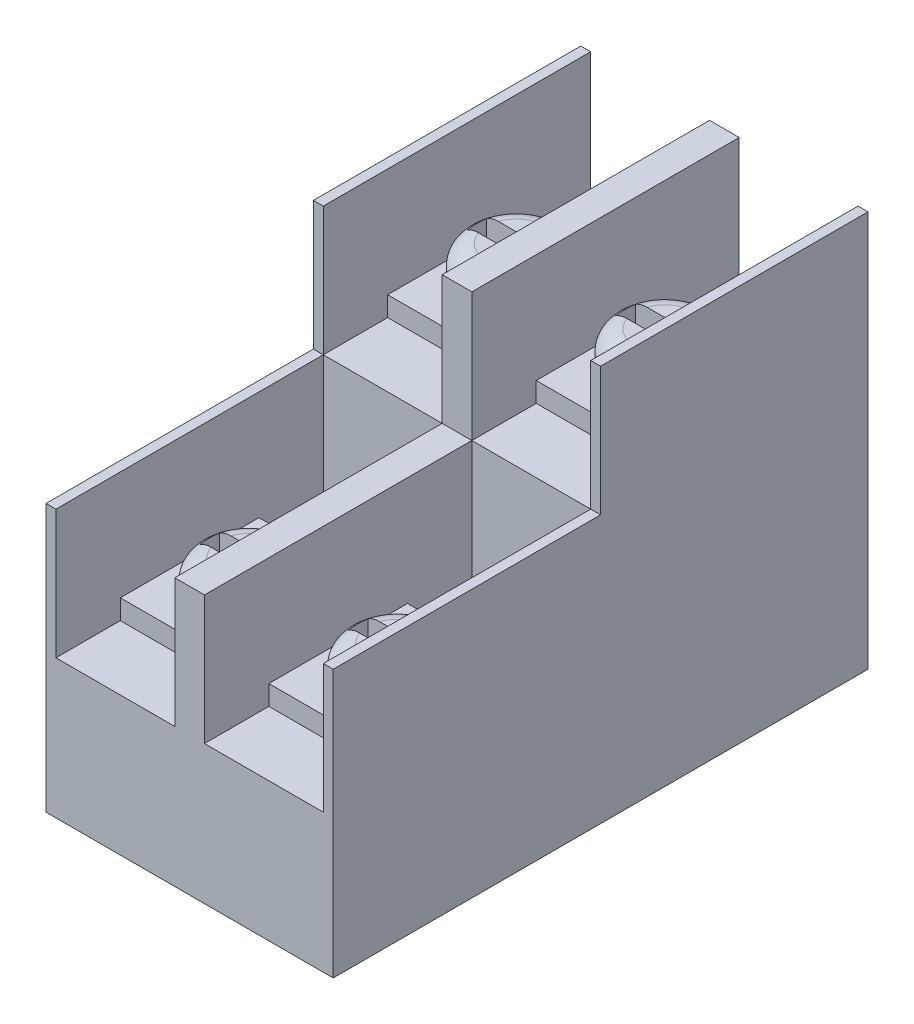
SolidWorks part; units mm, degrees
ref_plane "前视基准面" through (0, 0, 0) normal (0, 0, 1) x (1, 0, 0)
ref_plane "上视基准面" through (0, 0, 0) normal (0, 1, 0) x (1, 0, 0)
ref_plane "右视基准面" through (0, 0, 0) normal (1, 0, 0) x (0, 0, -1)
sketch "草图2" plane through (0, 0, 0) normal (0, 1, 0) x (1, 0, 0)
  line L1 (-7.25, -13.5) -> (7.25, -13.5)
  line L2 (-7.25, -13.5) -> (-7.25, 13.5)
  line L3 (-7.25, 13.5) -> (7.25, 13.5)
  line L4 (7.25, -13.5) -> (7.25, 13.5)
  line L5 (-7.25, -13.5) -> (7.25, 13.5) construction
  line L6 (-7.25, 13.5) -> (7.25, -13.5) construction
  point P0 (0, 0)
  dimension "D1" = 14.5
  dimension "D2" = 27
extrude "凸台-拉伸1" add sketch "草图2" along normal blind 20
sketch "草图3" plane through (7.25, 0, 0) normal (1, 0, 0) x (0, 0, -1)
  line L0 (0, 20) -> (0, 13.5)
  line L1 (-13.5, 20) -> (13.5, 20) construction
  line L2 (0, 13.5) -> (-13.5, 13.5)
  line L3 (-13.5, 20) -> (-13.5, 0) construction
  line L4 (-13.5, 13.5) -> (-13.5, 20)
  line L5 (-13.5, 20) -> (0, 20)
  line L6 (-13.5, 0) -> (13.5, 0) construction
  dimension "D1" = 13.5
extrude "切除-拉伸1" cut sketch "草图3" against normal through all
sketch "草图5" plane through (0, 20, 0) normal (0, 1, 0) x (1, 0, 0)
  line L0 (-7.25, 13.5) -> (-7.25, 0) construction
  line L1 (0.75, 13.5) -> (0.75, 0)
  line L2 (7.25, 13.5) -> (-7.25, 13.5) construction
  line L3 (-7.25, 0) -> (7.25, 0) construction
  line L4 (0.75, 0) -> (6.75, 0)
  line L5 (6.75, 0) -> (6.75, 13.5)
  line L6 (6.75, 13.5) -> (0.75, 13.5)
  line L7 (7.25, 0) -> (7.25, 13.5) construction
  line L8 (-0.75, 0) -> (-6.75, 0)
  line L9 (-6.75, 0) -> (-6.75, 13.5)
  line L10 (-6.75, 13.5) -> (-0.75, 13.5)
  line L11 (-0.75, 13.5) -> (-0.75, 0)
  line L17 (0, -1000) -> (0, 49000) construction
  dimension "D1" = 0.5
  dimension "D2" = 6
  dimension "D3" = 0.5
  dimension "D4" = 6
extrude "切除-拉伸2" cut sketch "草图5" against normal blind 6.5
sketch "草图7" plane through (0, 13.5, 0) normal (0, 1, 0) x (1, 0, 0)
  line L0 (6.75, 0) -> (6.75, -13.5)
  line L1 (-7.25, -13.5) -> (7.25, -13.5) construction
  line L2 (6.75, -13.5) -> (0.75, -13.5)
  line L3 (0.75, -13.5) -> (0.75, 0)
  line L4 (0.75, 0) -> (6.75, 0)
  line L5 (-6.75, 13.5) -> (-6.75, 0) construction
  line L6 (-6.75, -13.5) -> (-0.75, -13.5)
  line L7 (-6.75, 0) -> (-6.75, -13.5)
  line L8 (-0.75, 0) -> (-6.75, 0)
  line L9 (-0.75, -13.5) -> (-0.75, 0)
extrude "切除-拉伸4" cut sketch "草图7" against normal blind 6.5
sketch "草图8" plane through (0, 13.5, 0) normal (0, 1, 0) x (1, 0, 0)
  line L0 (-6.75, 13.5) -> (-6.75, 0) construction
  line L1 (-0.75, 0) -> (-0.75, 13.5) construction
  line L2 (-6.75, 10.25) -> (-0.75, 10.25)
  line L3 (-6.75, 10.25) -> (-6.75, 3.25)
  line L4 (-6.75, 3.25) -> (-0.75, 3.25)
  line L5 (-0.75, 10.25) -> (-0.75, 3.25)
  line L6 (0.75, 6.75) -> (13.2595, 6.75) construction
  line L7 (0.75, 13.5) -> (0.75, 0) construction
  line L9 (0.75, 10.25) -> (0.75, 3.25)
  line L10 (6.75, 3.25) -> (0.75, 3.25)
  line L11 (6.75, 10.25) -> (6.75, 3.25)
  line L12 (6.75, 10.25) -> (0.75, 10.25)
  line L13 (-3.75, 13.5) -> (-3.75, 1.5879) construction
  line L14 (-0.75, 13.5) -> (-6.75, 13.5) construction
  line L16 (6.75, 0) -> (6.75, 13.5) construction
  circle A0 centre (-3.75, 6.75) radius 1.75
  circle A1 centre (3.75, 6.75) radius 1.75
  point P29 (-0.75, 6.75)
  point P32 (3.75, 10.25)
  dimension "D2" = 3.5
  dimension "D1" = 7
extrude "凸台-拉伸3" add sketch "草图8" along normal blind 1
sketch "草图9" plane through (0, 7, 0) normal (0, 1, 0) x (1, 0, 0)
  line L0 (-6.75, 0) -> (-6.75, -13.5) construction
  line L1 (-6.75, -3.25) -> (-0.75, -3.25)
  line L2 (-6.75, -3.25) -> (-6.75, -10.25)
  line L3 (-6.75, -10.25) -> (-0.75, -10.25)
  line L4 (-0.75, -3.25) -> (-0.75, -10.25)
  line L5 (-0.75, -13.5) -> (-0.75, 0) construction
  line L6 (-6.75, 10.25) -> (-6.75, 3.25) construction
  line L7 (-3.75, 6.75) -> (-3.75, -14.6652) construction
  line L9 (0, 0) -> (-14.6212, 0) construction
  line L10 (-6.75, 3.25) -> (-0.75, 3.25) construction
  line L12 (6.75, -3.25) -> (6.75, -10.25)
  line L13 (6.75, -3.25) -> (0.75, -3.25)
  line L14 (0.75, -3.25) -> (0.75, -10.25)
  line L15 (6.75, -10.25) -> (0.75, -10.25)
  line L16 (0.75, 0) -> (0.75, -13.5) construction
  line L17 (6.75, -13.5) -> (6.75, 0) construction
  circle A0 centre (-3.75, -6.75) radius 1.75
  circle A1 centre (-3.75, 6.75) radius 1.75 construction
  circle A2 centre (3.75, -6.75) radius 1.75
  point P23 (-0.75, -6.75)
  point P38 (3.75, -3.25)
extrude "凸台-拉伸4" add sketch "草图9" along normal blind 1
sketch "草图10" plane through (0, 14.5, 0) normal (0, 1, 0) x (1, 0, 0)
  line L3 (0, 0) -> (0, 15.3782) construction
  circle A0 centre (3.75, 6.75) radius 2.5
  circle A1 centre (3.75, 6.75) radius 1.75 construction
  circle A2 centre (-3.75, 6.75) radius 2.5
  dimension "D1" = 5
extrude "凸台-拉伸5" add sketch "草图10" along normal blind 2
sketch "草图14" plane through (0, 8, 0) normal (0, 1, 0) x (1, 0, 0)
  line L0 (0, 0) -> (0, -10.3394) construction
  circle A0 centre (-3.75, -6.75) radius 2.5
  circle A1 centre (3.75, -6.75) radius 2.5
  dimension "D1" = 5
extrude "凸台-拉伸6" add sketch "草图14" along normal blind 1.5
sketch "草图15" plane through (0, 9.5, 0) normal (0, 1, 0) x (1, 0, 0)
  line L0 (3.25, -9.1995) -> (3.25, -7.25)
  line L1 (1.75, -6.25) -> (3.25, -6.25)
  line L2 (1.75, -6.25) -> (1.75, -7.25)
  line L3 (1.75, -7.25) -> (3.25, -7.25)
  line L4 (5.75, -6.25) -> (5.75, -7.25)
  line L5 (4.25, -4.3005) -> (4.25, -6.25)
  line L6 (-0.584, -6.75) -> (8.084, -6.75) construction
  line L7 (3.75, -10.7827) -> (3.75, -2.7173) construction
  line L8 (3.25, -6.25) -> (3.25, -4.3005)
  line L9 (4.25, -7.25) -> (4.25, -9.1995)
  line L10 (4.25, -7.25) -> (5.75, -7.25)
  line L11 (4.25, -6.25) -> (5.75, -6.25)
  line L13 (0, -1000) -> (0, 49000) construction
  line L14 (-3.75, -10.7827) -> (-3.75, -2.7173) construction
  line L15 (0.584, -6.75) -> (-8.084, -6.75) construction
  line L16 (-4.25, -6.25) -> (-5.75, -6.25)
  line L17 (-4.25, -7.25) -> (-5.75, -7.25)
  line L18 (-4.25, -7.25) -> (-4.25, -9.1995)
  line L19 (-3.25, -6.25) -> (-3.25, -4.3005)
  line L20 (-4.25, -4.3005) -> (-4.25, -6.25)
  line L21 (-5.75, -6.25) -> (-5.75, -7.25)
  line L22 (-1.75, -7.25) -> (-3.25, -7.25)
  line L23 (-1.75, -6.25) -> (-1.75, -7.25)
  line L24 (-1.75, -6.25) -> (-3.25, -6.25)
  line L25 (-3.25, -9.1995) -> (-3.25, -7.25)
  line L26 (0.75, 0) -> (0.75, -13.5) construction
  circle A0 centre (3.75, -6.75) radius 2.5 construction
  arc A1 (3.25, -9.1995) -> (4.25, -9.1995) centre (3.75, -6.75) ccw
  arc A3 (3.25, -4.3005) -> (4.25, -4.3005) centre (3.75, -6.75) cw
  arc A4 (-3.25, -4.3005) -> (-4.25, -4.3005) centre (-3.75, -6.75) ccw
  arc A5 (-3.25, -9.1995) -> (-4.25, -9.1995) centre (-3.75, -6.75) cw
  point P15 (3.75, -6.75)
  point P18 (3.75, -6.75)
  point P45 (0.75, -6.75)
  dimension "D1" = 4
  dimension "D2" = 1
  dimension "D3" = 1
fillet "圆角1" radius 1 4 edges at (-3.75, 16.5, -9.25) (3.75, 16.5, -4.25) (3.75, 9.5, 4.25) (-3.75, 9.5, 9.25)
extrude "切除-拉伸12" cut sketch "草图15" against normal blind 1.2
sketch "草图16" plane through (0, 16.5, 0) normal (0, 1, 0) x (1, 0, 0)
  line L0 (3.75, 6.75) -> (3.75, 9.8332) construction
  line L1 (3.75, 6.75) -> (10.8226, 6.75) construction
  line L2 (0, 0) -> (0, 17.5195) construction
  line L3 (-3.75, 6.75) -> (-10.8226, 6.75) construction
  line L4 (-3.75, 6.75) -> (-3.75, 9.8332) construction
  line L5 (-3.25, 7.25) -> (-1.75, 7.25)
  line L6 (-3.25, 9.1995) -> (-3.25, 7.25)
  line L7 (-4.25, 7.25) -> (-4.25, 9.1995)
  line L8 (-5.75, 7.25) -> (-4.25, 7.25)
  line L9 (-5.75, 6.25) -> (-5.75, 7.25)
  line L10 (-4.25, 6.25) -> (-5.75, 6.25)
  line L11 (-4.25, 4.2802) -> (-4.25, 6.25)
  line L12 (-3.25, 6.25) -> (-3.25, 4.2802)
  line L13 (-1.75, 6.25) -> (-3.25, 6.25)
  line L14 (-1.75, 7.25) -> (-1.75, 6.25)
  line L40 (1.75, 7.25) -> (1.75, 6.25)
  line L41 (1.75, 6.25) -> (3.25, 6.25)
  line L42 (3.25, 6.25) -> (3.25, 4.2802)
  line L43 (4.25, 4.2802) -> (4.25, 6.25)
  line L44 (4.25, 6.25) -> (5.75, 6.25)
  line L45 (5.75, 6.25) -> (5.75, 7.25)
  line L46 (5.75, 7.25) -> (4.25, 7.25)
  line L47 (4.25, 7.25) -> (4.25, 9.1995)
  line L48 (3.25, 9.1995) -> (3.25, 7.25)
  line L49 (3.25, 7.25) -> (1.75, 7.25)
  arc A0 (-4.25, 9.1995) -> (-3.25, 9.1995) centre (-3.75, 6.75) cw
  arc A1 (-3.25, 4.2802) -> (-4.25, 4.2802) centre (-3.75, 6.75) cw
  arc A8 (3.25, 4.2802) -> (4.25, 4.2802) centre (3.75, 6.75) ccw
  arc A9 (4.25, 9.1995) -> (3.25, 9.1995) centre (3.75, 6.75) ccw
  circle A12 centre (3.75, 6.75) radius 2.5 construction
  dimension "D1" = 1
  dimension "D2" = 1
  dimension "D3" = 4
extrude "切除-拉伸13" cut sketch "草图16" against normal blind 1.2
sketch "草图17" plane through (0, 0, 0) normal (0, -1, 0) x (1, 0, 0)
  circle A0 centre (3.75, 6.75) radius 0.5
  circle A1 centre (-3.75, 6.75) radius 0.5
  circle A2 centre (-3.75, -6.75) radius 0.5
  circle A3 centre (3.75, -6.75) radius 0.5
  dimension "D1" = 1
extrude "凸台-拉伸7" add sketch "草图17" along normal blind 3
sketch "草图11" plane through (0, 13.5, 0) normal (0, 1, 0) x (1, 0, 0)
  line L0 (-0.75, 0) -> (-0.75, 3.25) construction
  line L1 (-6.75, 12.5) -> (-0.75, 12.5)
  line L2 (-6.75, 12.5) -> (-6.75, 4.5)
  line L3 (-6.75, 4.5) -> (-0.75, 4.5)
  line L4 (-0.75, 12.5) -> (-0.75, 4.5)
  line L5 (-6.75, 13.5) -> (-6.75, 0) construction
  line L6 (-0.75, 13.5) -> (-6.75, 13.5) construction
  line L8 (7, 12.5) -> (0.75, 12.5)
  line L9 (7, 12.5) -> (7, 4.5)
  line L10 (7, 4.5) -> (0.75, 4.5)
  line L11 (0.75, 12.5) -> (0.75, 4.5)
  dimension "D1" = 1
  dimension "D2" = 8
extrude "切除-拉伸7" [suppressed] cut sketch "草图11" against normal blind 3
sketch "草图13" [suppressed] plane through (0, 7, 0) normal (0, 1, 0) x (1, 0, 0)
  line L0 (-7, 0) -> (-7, -13.5) construction
  line L1 (-0.75, -13.5) -> (-0.75, 0) construction
  line L2 (-7, -1) -> (-0.75, -1)
  line L3 (-7, -1) -> (-7, -9)
  line L4 (-7, -9) -> (-0.75, -9)
  line L5 (-0.75, -1) -> (-0.75, -9)
  line L6 (-7, 12.5) -> (-7, 4.5) construction
  line L7 (-0.75, 0) -> (-7, 0) construction
  line L8 (0, 0) -> (0, -50000) construction
  line L9 (0.75, -1) -> (0.75, -9)
  line L10 (7, -9) -> (0.75, -9)
  line L11 (7, -1) -> (7, -9)
  line L12 (7, -1) -> (0.75, -1)
  dimension "D1" = 1
extrude "切除-拉伸8" [suppressed] cut sketch "草图13" against normal blind 3
